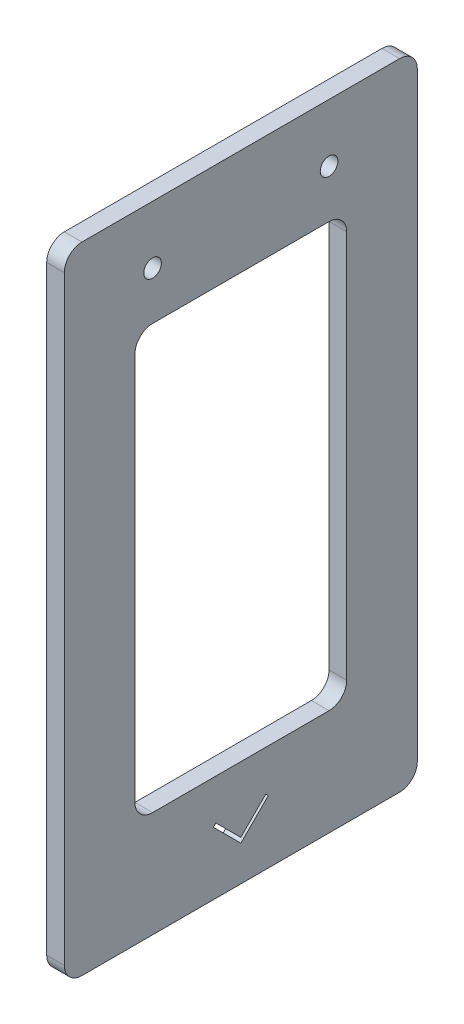
SolidWorks part; units mm, degrees
material "Balsa"
ref_plane "Front Plane" through (0, 0, 0) normal (0, 0, 1) x (1, 0, 0)
ref_plane "Top Plane" through (0, 0, 0) normal (0, 1, 0) x (1, 0, 0)
ref_plane "Right Plane" through (0, 0, 0) normal (1, 0, 0) x (0, 0, -1)
sketch "Sketch3" plane through (0, 0, 0) normal (1, 0, 0) x (0, 0, -1)
  line L0 (-31.75, -76.2) -> (31.75, -76.2)
  line L1 (-57.15, -114.3) -> (57.15, -114.3)
  line L2 (-63.5, -107.95) -> (-63.5, 107.95)
  line L3 (-57.15, 114.3) -> (57.15, 114.3)
  line L4 (63.5, -107.95) -> (63.5, 107.95)
  line L5 (-63.5, -114.3) -> (63.5, 114.3) construction
  line L6 (-63.5, 114.3) -> (63.5, -114.3) construction
  line L8 (-38.1, -69.85) -> (-38.1, 69.85)
  line L9 (-31.75, 76.2) -> (31.75, 76.2)
  line L11 (0, 0) -> (38.1, 76.2) construction
  line L12 (-38.1, 76.2) -> (0, 0) construction
  line L13 (38.1, -69.85) -> (38.1, 69.85)
  arc A0 (-57.15, -114.3) -> (-63.5, -107.95) centre (-57.15, -107.95) cw
  arc A1 (63.5, -107.95) -> (57.15, -114.3) centre (57.15, -107.95) cw
  arc A2 (63.5, 107.95) -> (57.15, 114.3) centre (57.15, 107.95) ccw
  arc A3 (-63.5, 107.95) -> (-57.15, 114.3) centre (-57.15, 107.95) cw
  arc A4 (31.75, -76.2) -> (38.1, -69.85) centre (31.75, -69.85) ccw
  arc A5 (-31.75, -76.2) -> (-38.1, -69.85) centre (-31.75, -69.85) cw
  arc A6 (31.75, 76.2) -> (38.1, 69.85) centre (31.75, 69.85) cw
  arc A7 (-38.1, 69.85) -> (-31.75, 76.2) centre (-31.75, 69.85) cw
  point P0 (0, 0)
  point P6 (0, 0)
  point P26 (38.1, -76.2)
  dimension "D7" = 6.35
  dimension "D8" = 6.35
  dimension "D1" = 228.6
  dimension "D2" = 127
  dimension "D3" = 76.2
  dimension "D4" = 152.4
  dimension "D5" = 38.1
  dimension "D6" = 25.4
extrude "Boss-Extrude2" add sketch "Sketch3" along normal blind 6.35
sketch "Sketch4" plane through (6.35, 0, 0) normal (1, 0, 0) x (0, 0, -1)
  line L5 (0, -99.8039) -> (-8.9803, -90.8237)
  line L6 (-8.9803, -90.8237) -> (-9.8783, -91.7217)
  line L8 (-9.8783, -91.7217) -> (0, -101.6)
  line L9 (0, -101.6) -> (9.8783, -91.7217)
  line L10 (9.8783, -91.7217) -> (8.9803, -90.8237)
  line L11 (8.9803, -90.8237) -> (0, -99.8039)
  line L12 (0, 55) -> (0, -55) construction
  line L13 (-57.15, -114.3) -> (57.15, -114.3) construction
  dimension "D1" = 12.7
  dimension "D2" = 12.7
  dimension "D3" = 1.27
extrude "Cut-Extrude1" cut sketch "Sketch4" against normal up to next
sketch "Sketch5" plane through (6.35, 0, 0) normal (1, 0, 0) x (0, 0, -1)
  line L0 (-57.15, -114.3) -> (57.15, -114.3) construction
  line L1 (-63.5, 93.472) -> (-31.75, 93.472) construction
  line L2 (-63.5, 107.95) -> (-63.5, -107.95) construction
  line L3 (-31.75, 93.472) -> (31.75, 93.472) construction
  line L4 (-31.75, 93.472) -> (31.75, 93.472) construction
  line L5 (31.75, 93.472) -> (63.5, 93.472) construction
  line L6 (63.5, -107.95) -> (63.5, 107.95) construction
  line L7 (-108.1488, 76.2) -> (105.3076, 76.2) construction
  line L8 (31.75, 76.2) -> (-31.75, 76.2) construction
  line L9 (0, 55) -> (0, -55) construction
  circle A0 centre (-31.75, 93.472) radius 3.175
  circle A1 centre (31.75, 93.472) radius 3.175
  point P16 (0, 93.472)
  dimension "D3" = 6.35
  dimension "D4" = 6.35
  dimension "D1" = 63.5
  dimension "D5" = 207.772
extrude "Cut-Extrude2" cut sketch "Sketch5" against normal through all both and the other way through all
